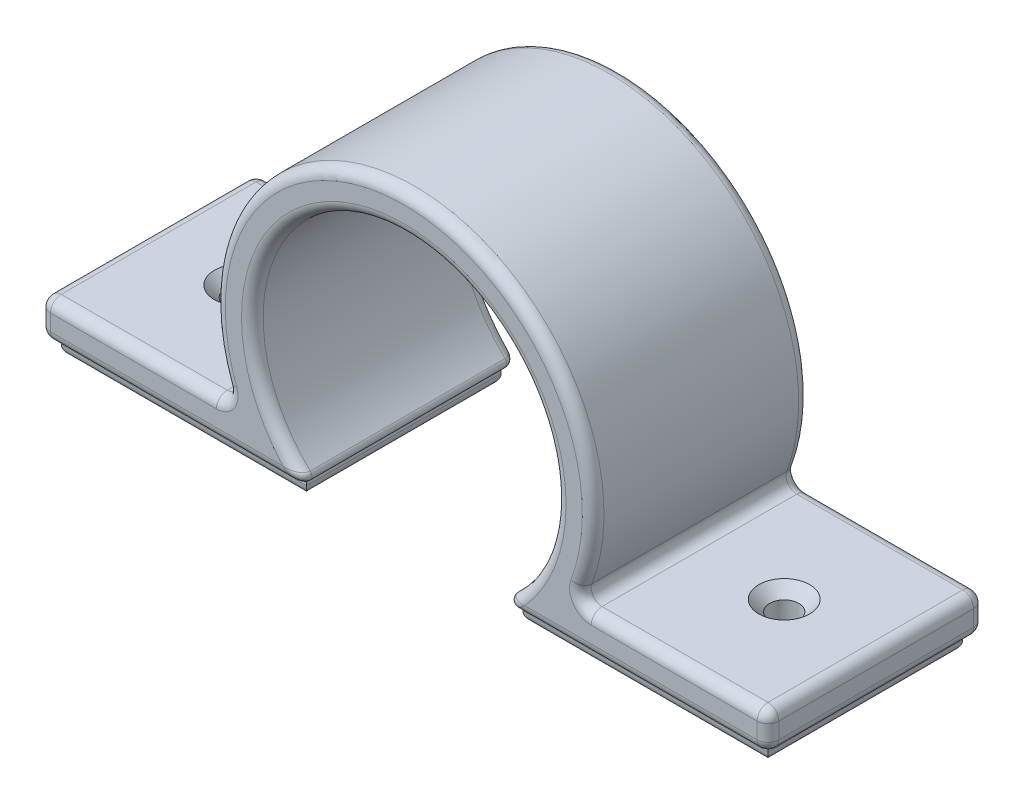
SolidWorks part; units mm, degrees
material "ABS"
ref_plane "Front Plane" through (0, 0, 0) normal (0, 0, 1) x (1, 0, 0)
ref_plane "Top Plane" through (0, 0, 0) normal (0, 1, 0) x (1, 0, 0)
ref_plane "Right Plane" through (0, 0, 0) normal (1, 0, 0) x (0, 0, -1)
sketch "Sketch2" plane through (0, 0, 0) normal (0, 0, 1) x (1, 0, 0)
  line L0 (-33.6603, -11) -> (-8.6603, -11)
  line L1 (8.6603, -11) -> (33.6603, -11)
  line L2 (15.8114, -7.5) -> (33.6603, -7.5)
  line L3 (-33.6603, -7.5) -> (-15.8114, -7.5)
  line L4 (-33.6603, -7.5) -> (-33.6603, -11)
  line L5 (33.6603, -7.5) -> (33.6603, -11)
  arc A0 (8.6603, -11) -> (-8.6603, -11) centre (0, 0) ccw
  arc A1 (15.8114, -7.5) -> (-15.8114, -7.5) centre (0, 0) ccw
  point P6 (0, -14)
  dimension "D1" = 28
  dimension "D2" = 3
  dimension "D3" = 25
  dimension "D4" = 3.5
extrude "Boss-Extrude1" add sketch "Sketch2" along normal mid plane 20
fillet "Fillet1" radius 0.5 2 edges at (8.6603, -11, 0) (-8.6603, -11, 0)
sketch "Sketch3" plane through (0, -7.5, 0) normal (0, 1, 0) x (1, 0, 0)
  line L1 (-15.8114, -10) -> (-33.6603, -10) construction
  line L2 (0, -11) -> (0, 11) construction
  line L4 (-33.6603, -10) -> (-33.6603, 10) construction
  circle A0 centre (-25.1603, 0) radius 1.35
  circle A1 centre (25.1603, 0) radius 1.35
  point P3 (0, 0)
  point P10 (0, 0)
  dimension "D1" = 2.7
  dimension "D2" = 8.5
  dimension "D3" = 10
extrude "Cut-Extrude1" cut sketch "Sketch3" against normal through all
fillet "Fillet2" radius 1 26 edges at (33.6603, -11, 0) (33.6603, -7.5, 0) (-33.6603, -7.5, 0) (-33.6603, -11, 0) (33.6603, -9.25, -10) (24.7358, -7.5, -10) (0, 17.5, -10) (-24.7358, -7.5, -10) (-33.6603, -9.25, -10) (-21.8301, -11, -10) (-9.5358, -10.6857, -10) (0, 14, -10) (9.5358, -10.6857, -10) (21.8301, -11, -10) (-9.5358, -10.6857, 10) (-21.8301, -11, 10) (-33.6603, -9.25, 10) (-24.7358, -7.5, 10) (0, 17.5, 10) (24.7358, -7.5, 10) (33.6603, -9.25, 10) (21.8301, -11, 10) (9.5358, -10.6857, 10) (0, 14, 10) (-15.8114, -7.5, 0) (15.8114, -7.5, 0)
chamfer "Chamfer1" distance 1 angle 45 2 edges at (-25.1603, -7.5, 1.35) (25.1603, -7.5, -1.35)
sketch "Sketch4" plane through (0, -11, 0) normal (0, -1, 0) x (1, 0, 0)
  line L4 (-32.6603, 9) -> (-32.6603, -9)
  line L5 (-10, -9) -> (-10, 9)
  line L6 (-32.6603, 9) -> (-32.6603, -9)
  line L7 (-32.6603, -9) -> (-10, -9)
  line L9 (-10, -9) -> (-10, 9)
  line L12 (10, -9) -> (32.6603, -9)
  line L13 (10, 9) -> (10, -9)
  line L14 (10, -9) -> (32.6603, -9)
  line L15 (32.6603, -9) -> (32.6603, 9)
  line L17 (10, 9) -> (10, -9)
  line L20 (-32.6603, -9) -> (-10, -9)
  line L21 (-10, 9) -> (-32.6603, 9)
  line L22 (-10, 9) -> (-32.6603, 9)
  line L23 (32.6603, -9) -> (32.6603, 9)
  line L24 (32.6603, 9) -> (10, 9)
  line L25 (32.6603, 9) -> (10, 9)
  dimension "D1" = 0
  dimension "D2" = 0
extrude "Boss-Extrude2" add sketch "Sketch4" along normal blind 1.5
fillet "Fillet3" radius 1 8 edges at (32.6603, -12.5, 0) (21.3301, -12.5, -9) (10, -12.5, 0) (21.3301, -12.5, 9) (-32.6603, -12.5, 0) (-21.3301, -12.5, 9) (-10, -12.5, 0) (-21.3301, -12.5, -9)
